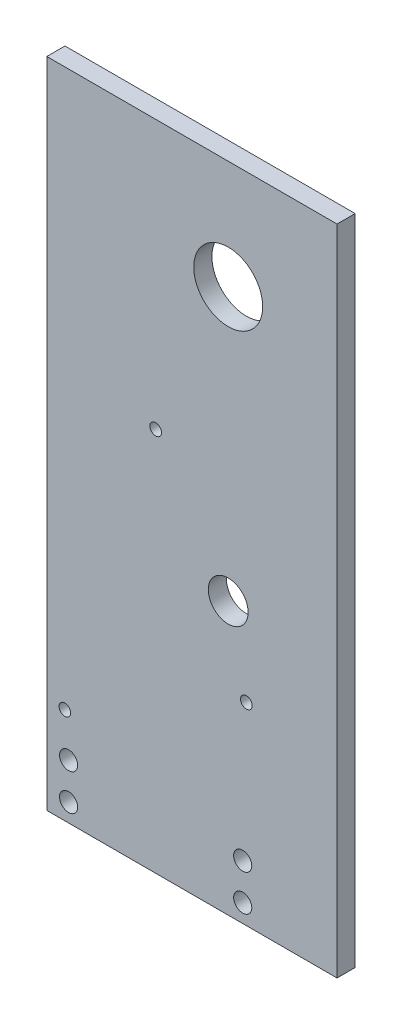
SolidWorks part; units mm, degrees
material "Thornel Mat VMA"
ref_plane "Front Plane" through (0, 0, 0) normal (0, 0, 1) x (1, 0, 0)
ref_plane "Top Plane" through (0, 0, 0) normal (0, 1, 0) x (1, 0, 0)
ref_plane "Right Plane" through (0, 0, 0) normal (1, 0, 0) x (0, 0, -1)
sketch "Sketch1" plane through (0, 0, 0) normal (0, 0, 1) x (1, 0, 0)
  line L0 (0, 103.759) -> (0, -103.759) construction
  line L1 (-30, 76) -> (50, 76)
  line L2 (-30, 76) -> (-30, 256)
  line L3 (-30, 256) -> (50, 256)
  line L4 (50, 76) -> (50, 256)
  circle A0 centre (20, 226) radius 9.5
  dimension "D1" = 150
  dimension "D5" = 19
  dimension "D2" = 20
  dimension "D3" = 180
  dimension "D4" = 80
extrude "Boss-Extrude1" add sketch "Sketch1" along normal blind 5
sketch "Sketch2" plane through (0, 0, 5) normal (0, 0, 1) x (1, 0, 0)
  line L0 (20, 226) -> (20, 151) construction
  line L1 (20, 226) -> (-17.1819, 226) construction
  circle A0 centre (20, 151) radius 5.5
  dimension "D3" = 11
  dimension "D1" = 75
  dimension "D2" = 90
extrude "Cut-Extrude1" cut sketch "Sketch2" against normal blind 30
sketch "Sketch3" plane through (0, 0, 5) normal (0, 0, 1) x (1, 0, 0)
  circle A0 centre (0, 182) radius 1.6
  circle A1 centre (25, 129.3013) radius 1.6
  circle A2 centre (-25.0329, 102.5335) radius 1.6
  circle A3 centre (-24, 81) radius 2.5
  circle A4 centre (24, 81) radius 2.5
  circle A5 centre (24, 91) radius 2.5
  circle A6 centre (-24, 91) radius 2.5
  dimension "D1" = 5
  dimension "D2" = 3.2
extrude "Cut-Extrude2" cut sketch "Sketch3" against normal blind 5
